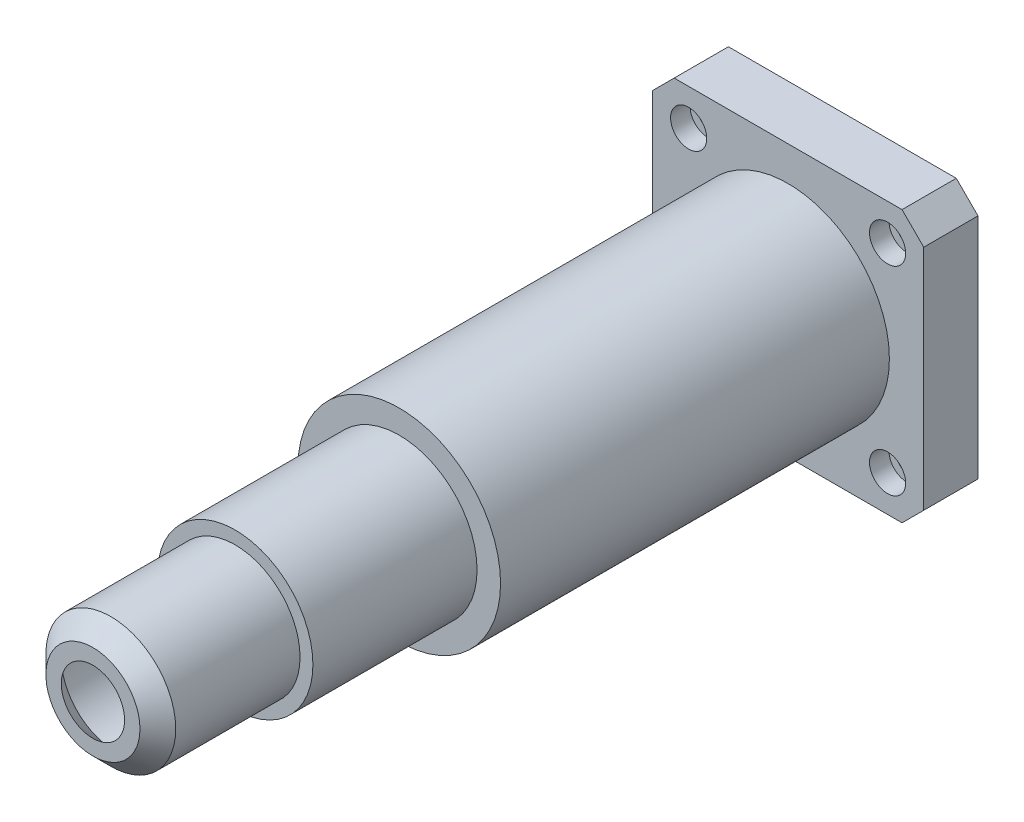
SolidWorks part; units mm, degrees
material "AISI Type 316L stainless steel"
ref_plane "Front Plane" through (0, 0, 0) normal (0, 0, 1) x (1, 0, 0)
ref_plane "Top Plane" through (0, 0, 0) normal (0, 1, 0) x (1, 0, 0)
ref_plane "Right Plane" through (0, 0, 0) normal (1, 0, 0) x (0, 0, -1)
sketch "Sketch1" plane through (0, 0, 0) normal (0, 0, 1) x (1, 0, 0)
  line L1 (-37.5, -37.5) -> (37.5, -37.5)
  line L2 (-37.5, -37.5) -> (-37.5, 37.5)
  line L3 (-37.5, 37.5) -> (37.5, 37.5)
  line L4 (37.5, -37.5) -> (37.5, 37.5)
  line L5 (-37.5, -37.5) -> (37.5, 37.5) construction
  line L6 (-37.5, 37.5) -> (37.5, -37.5) construction
  point P0 (0, 0)
  dimension "D1" = 75
extrude "Boss-Extrude1" add sketch "Sketch1" along normal blind 15
sketch "Sketch2" plane through (0, 0, 0) normal (0, 0, -1) x (-1, 0, 0)
  circle A0 centre (0, 0) radius 22
  dimension "D1" = 44
extrude "Boss-Extrude2" add sketch "Sketch2" along normal blind 5
sketch "Sketch3" plane through (0, 0, 0) normal (1, 0, 0) x (0, 0, -1)
  line L0 (-15, 28) -> (-122.5, 28)
  line L1 (-122.5, 28) -> (-122.5, 21.5)
  line L2 (-122.5, 21.5) -> (-167.8827, 21.5)
  line L3 (-167.8827, 21.5) -> (-167.8827, 17.9449)
  line L4 (-167.8827, 17.9449) -> (-202.2551, 17.9449)
  line L5 (-202.2551, 17.9449) -> (-207.2, 13)
  line L6 (-207.2, 13) -> (-207.2, 0)
  line L7 (-207.2, 0) -> (0, 0) construction
  line L8 (-15, 28) -> (-15, 0)
  line L9 (-15, -37.5) -> (-15, 37.5) construction
  line L10 (5, -22) -> (5, 22) construction
  line L11 (-207.2, 0) -> (-15, 0)
  dimension "D1" = 212.2
  dimension "D2" = 28
  dimension "D3" = 21.5
  dimension "D4" = 13
  dimension "D5" = 84.7
  dimension "D6" = 45
revolve "Revolve1" add sketch "Sketch3" angle 360 about L7
hole_wizard "CBORE for M5 Hex Socket Head Cap Screw1" positions "Sketch4" profile "Sketch5" counterbore size "M5" standard "ISO" end condition through all
sketch "Sketch4" plane through (0, 0, 15) normal (0, 0, 1) x (1, 0, 0)
  line L0 (37.5, 37.5) -> (-37.5, 37.5) construction
  line L1 (-37.5, 37.5) -> (-37.5, -37.5) construction
  point P0 (-27.5, 27.5)
  dimension "D1" = 10
  dimension "D2" = 10
sketch "Sketch5" plane through (-27.5, 27.5, 15) normal (1, 0, 0) x (0, -1, 0)
  line L0 (0, 0) -> (0, 20)
  line L1 (0, 20) -> (2.75, 20)
  line L3 (2.75, 20) -> (2.75, 5.4)
  line L4 (2.75, 5.4) -> (5, 5.4)
  line L5 (5, 5.4) -> (5, 0)
  line L7 (5, 0) -> (0, 0)
  line L11 (0, -6.35) -> (0, 107.95) construction
  dimension "Thru Hole Dia." = 5.5
  dimension "Thru Hole Depth" = 20
  dimension "C'Bore Dia." = 10
  dimension "C'Bore Depth" = 5.4
pattern_circular "CirPattern1" count 4 over 360 about axis through (0, 0, 15) along (0, 0, 1) of "CBORE for M5 Hex Socket Head Cap Screw1"
chamfer "Chamfer1" distance 6 angle 45 4 edges at (37.5, -37.5, 7.5) (-37.5, -37.5, 7.5) (37.5, 37.5, 7.5) (-37.5, 37.5, 7.5)
shell "Shell1" thickness 3 removed face at (-22, 0, -5) removed face at (13, 0, 207.2)
